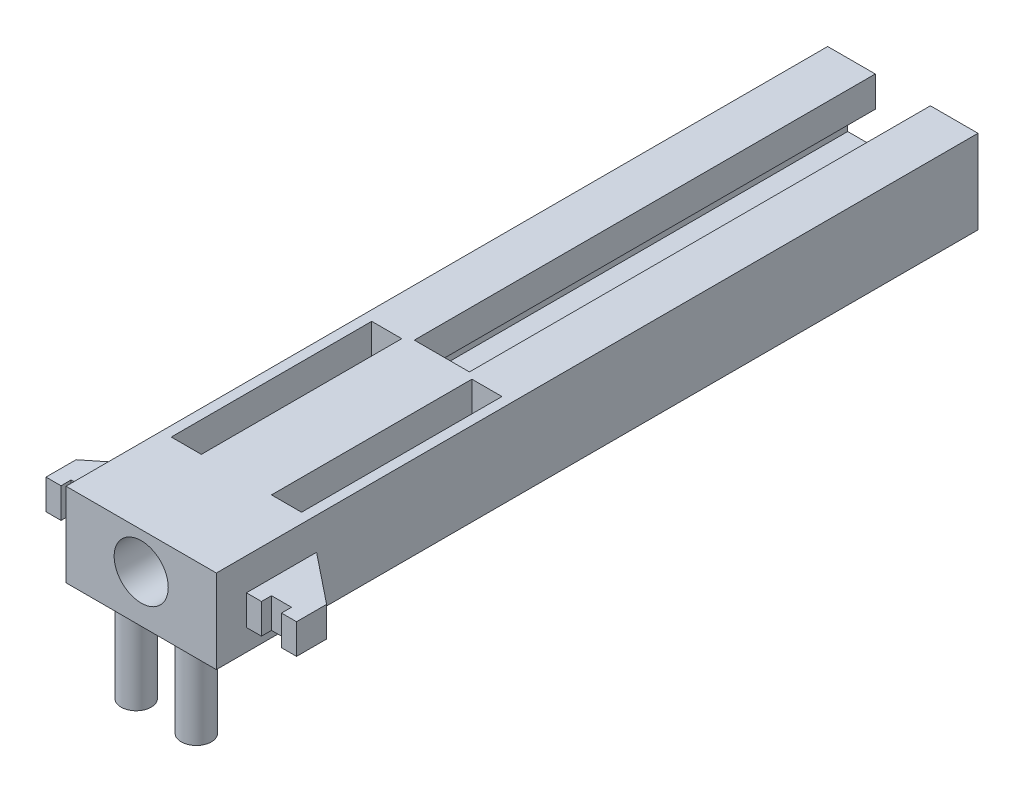
SolidWorks part; units mm, degrees
ref_plane "Front Plane" through (0, 0, 0) normal (0, 0, 1) x (1, 0, 0)
ref_plane "Top Plane" through (0, 0, 0) normal (0, 1, 0) x (1, 0, 0)
ref_plane "Right Plane" through (0, 0, 0) normal (1, 0, 0) x (0, 0, -1)
sketch "Sketch9" plane through (0, 0, 0) normal (0, 0, 1) x (1, 0, 0)
  line L1 (-7.5, 8.35) -> (7.5, 8.35)
  line L2 (-7.5, 8.35) -> (-7.5, 0)
  line L3 (-7.5, 0) -> (7.5, 0)
  line L4 (7.5, 8.35) -> (7.5, 0)
  line L5 (-7.5, 8.35) -> (7.5, 0) construction
  line L6 (-7.5, 0) -> (7.5, 8.35) construction
  point P0 (0, 4.175)
  point P19 (0, 0)
  dimension "D1" = 8.35
  dimension "D2" = 15
extrude "Boss-Extrude4" add sketch "Sketch9" along normal blind 76
sketch "Sketch7" plane through (0, 0, 0) normal (0, 0, 1) x (1, 0, 0)
  line L0 (-5.5, 2) -> (-5.5, 5.3)
  line L1 (-5.5, 5.3) -> (-2.75, 5.3)
  line L2 (-2.75, 5.3) -> (-2.75, 8.35)
  line L3 (-2.75, 8.35) -> (2.75, 8.35) construction
  line L4 (2.75, 8.35) -> (2.75, 5.3)
  line L5 (2.75, 5.3) -> (5.5, 5.3)
  line L6 (5.5, 5.3) -> (5.5, 2)
  line L7 (5.5, 2) -> (-5.5, 2)
  line L9 (7.5, 8.35) -> (-7.5, 8.35) construction
  line L11 (7.5, 0) -> (7.5, 8.35) construction
  line L13 (-2.75, 8.35) -> (2.75, 8.35)
  dimension "D1" = 3.3
  dimension "D2" = 2
  dimension "D3" = 11
  dimension "D4" = 5.5
  dimension "D5" = 2
extrude "Cut-Extrude4" cut sketch "Sketch7" along normal blind 46
sketch "Sketch10" plane through (0, 0, 76) normal (0, 0, 1) x (1, 0, 0)
  line L0 (5.5, 2) -> (-5.5, 2) construction
  circle A0 centre (0, 4.7) radius 2.7
  dimension "D1" = 5.4
extrude "Cut-Extrude5" cut sketch "Sketch10" against normal up to surface (30 mm away) up to face at (0, 5.2375, 46)
sketch "Sketch12" plane through (7.5, 0, 0) normal (1, 0, 0) x (0, 0, -1)
  line L0 (-76, 0) -> (0, 0) construction
  line L1 (-73, 5.14) -> (-70, 5.14)
  line L2 (-73, 5.14) -> (-73, 2.14)
  line L3 (-73, 2.14) -> (-70, 2.14)
  line L4 (-70, 5.14) -> (-70, 2.14)
  line L5 (-73, 5.14) -> (-70, 2.14) construction
  line L6 (-73, 2.14) -> (-70, 5.14) construction
  line L7 (-76, 0) -> (-76, 8.35) construction
  point P0 (-71.5, 3.64)
  dimension "D1" = 3
  dimension "D2" = 3
  dimension "D3" = 2.14
  dimension "D4" = 3
extrude "Boss-Extrude5" add sketch "Sketch12" along normal blind 5
ref_plane "Plane1" through (0, 0, 0) normal (1, 0, 0) x (0, 0, -1)
sketch "Sketch13" plane through (0, 0, 73) normal (0, 0, 1) x (1, 0, 0)
  line L1 (9, 5.14) -> (11, 5.14)
  line L2 (9, 5.14) -> (9, 2.14)
  line L3 (9, 2.14) -> (11, 2.14)
  line L4 (11, 5.14) -> (11, 2.14)
  line L6 (12.5, 5.14) -> (7.5, 5.14) construction
  line L7 (12.5, 2.14) -> (7.5, 2.14) construction
  point P8 (10, 5.14)
  point P9 (10, 5.14)
  dimension "D2" = 2
extrude "Cut-Extrude6" cut sketch "Sketch13" against normal blind 1
mirror "Mirror2" about plane through (0, 0, 0) normal (1, 0, 0) of "Boss-Extrude5"
mirror "Mirror4" about plane through (0, 0, 0) normal (1, 0, 0) of "Cut-Extrude6"
sketch "Sketch14" plane through (0, 5.14, 0) normal (0, 1, 0) x (1, 0, 0)
  line L0 (12.5, -70) -> (7.5, -66)
  line L1 (7.5, -76) -> (7.5, 0) construction
  line L2 (7.5, -66) -> (7.5, -70)
  line L3 (7.5, -70) -> (12.5, -70)
  dimension "D1" = 4
extrude "Boss-Extrude6" add sketch "Sketch14" against normal up to surface (3 mm away) up to face at (10, 2.14, 72)
mirror "Mirror5" about plane through (0, 0, 0) normal (1, 0, 0) of "Boss-Extrude6"
sketch "Sketch15" plane through (0, 8.35, 0) normal (0, 1, 0) x (1, 0, 0)
  line L0 (-7.5, -76) -> (-7.5, 0) construction
  line L1 (-6.5, -66.5) -> (-3.5, -66.5)
  line L2 (-6.5, -66.5) -> (-6.5, -46.5)
  line L3 (-6.5, -46.5) -> (-3.5, -46.5)
  line L4 (-3.5, -66.5) -> (-3.5, -46.5)
  line L5 (-6.5, -66.5) -> (-3.5, -46.5) construction
  line L6 (-6.5, -46.5) -> (-3.5, -66.5) construction
  line L7 (2.75, -46) -> (-2.75, -46) construction
  point P0 (-5, -56.5)
  point P11 (-5, -46.5)
  dimension "D1" = 20
  dimension "D2" = 3
  dimension "D3" = 1
  dimension "D4" = 0.5
extrude "Cut-Extrude7" cut sketch "Sketch15" against normal up to next
mirror "Mirror6" about plane through (0, 0, 0) normal (1, 0, 0) of "Cut-Extrude7"
sketch "Sketch16" plane through (0, 0, 0) normal (0, -1, 0) x (1, 0, 0)
  line L0 (0, -35.8636) -> (0, 35.8636) construction
  line L1 (-7.5, 76) -> (7.5, 76) construction
  circle A0 centre (0, 69) radius 2.5
  dimension "D1" = 5
  dimension "D2" = 7
extrude "Cut-Extrude8" cut sketch "Sketch16" against normal up to surface (2 mm away) up to face at (2.7, 4.7, 76)
sketch "Sketch17" plane through (0, 0, 0) normal (0, -1, 0) x (1, 0, 0)
  line L1 (-7.5, 76) -> (7.5, 76) construction
  line L2 (0, 76) -> (0, 0) construction
  line L3 (-7.5, 76) -> (-7.5, 0) construction
  circle A0 centre (-3, 73.5) radius 1.5
  circle A1 centre (3, 73.5) radius 1.5
  point P2 (0, 0)
  dimension "D1" = 3
  dimension "D2" = 4.5
  dimension "D3" = 2.5
extrude "Boss-Extrude7" add sketch "Sketch17" along normal up to surface (9 mm away)
